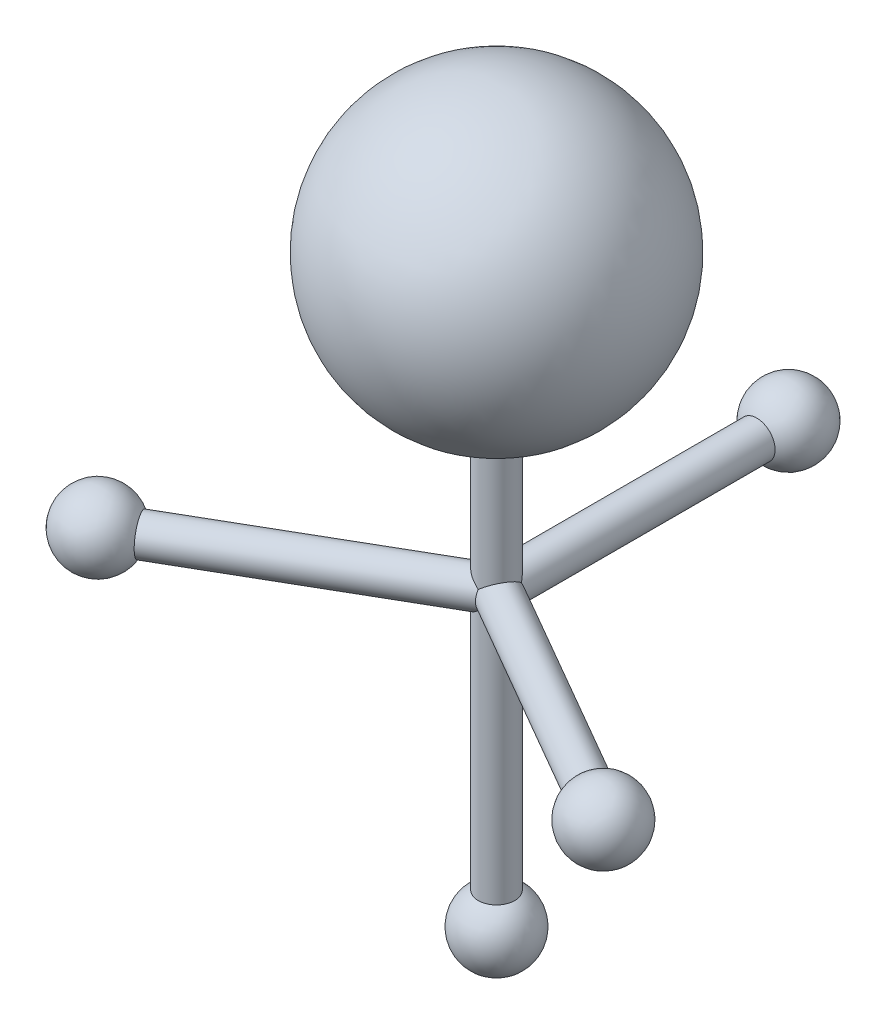
SolidWorks part; units mm, degrees
other "相机1"
ref_plane "前视基准面" through (0, 0, 0) normal (0, 0, 1) x (1, 0, 0)
ref_plane "上视基准面" through (0, 0, 0) normal (0, 1, 0) x (1, 0, 0)
ref_plane "右视基准面" through (0, 0, 0) normal (1, 0, 0) x (0, 0, -1)
sketch "草图1" plane through (0, 0, 0) normal (0, 1, 0) x (1, 0, 0)
  line L0 (0, 0) -> (0, 40)
  dimension "D4" = 40
revolve "杆件1" add sketch "草图1" angle 360 about L0 wall 2.5
sketch "草图4" plane through (0, 0, -40) normal (0, 0, -1) x (-1, 0, 0)
  line L0 (0, -1000) -> (0, 49000) construction
  circle A0 centre (0, 0) radius 5
  dimension "D1" = 10
revolve "标记点1" add sketch "草图4" angle 360 about L0 region at (-0.1118, -3.75, -40) region at (-1.061, 0, -40)
sketch "旋转轴" plane through (0, 0, 0) normal (0, 0, 1) x (1, 0, 0)
  line L0 (0, -1000) -> (0, 49000) construction
pattern_circular "阵列(圆周)杆件" count 3 over 360 about axis through (0, -1000, 0) along (0, 1, 0) of "杆件1"
pattern_circular "阵列(圆周)标记点" count 3 over 360 about axis through (0, -1000, 0) along (0, 1, 0) of "标记点1"
sketch "草图5" plane through (0, 0, 0) normal (0, 1, 0) x (1, 0, 0)
  circle A0 centre (0, 0) radius 2.5
  dimension "D1" = 5
extrude "杆件2" add sketch "草图5" along normal blind 40 and the other way blind 40
sketch "草图6" plane through (0, -40, 0) normal (0, -1, 0) x (1, 0, 0)
  line L0 (0, -1000) -> (0, 49000) construction
  circle A0 centre (0, 0) radius 5
  dimension "D1" = 10
revolve "标记点2" add sketch "草图6" angle 360 about L0 region at (-4.8882, -40, 0) region at (-1.061, -40, 0)
sketch "草图7" plane through (0, 40, 0) normal (0, 1, 0) x (1, 0, 0)
  line L0 (0, -1000) -> (0, 49000) construction
  circle A0 centre (0, 0) radius 20
  dimension "D1" = 40
revolve "旋转4" add sketch "草图7" angle 360 about L0 region at (8.6062, 40, 0) region at (1.061, 40, 0)
